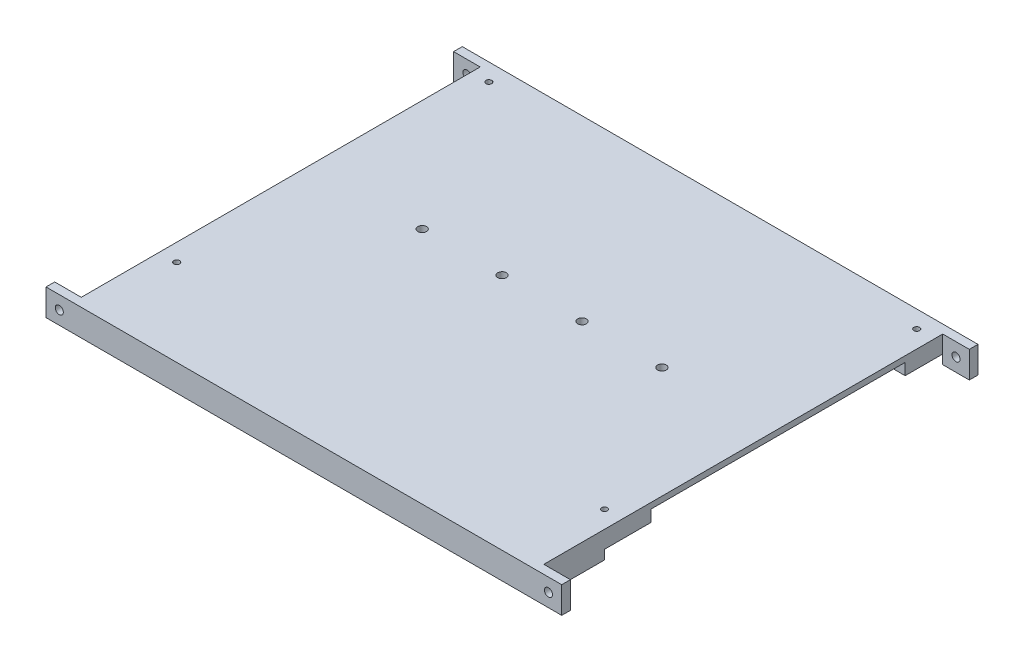
SolidWorks part; units mm, degrees
ref_plane "前视基准面" through (0, 0, 0) normal (0, 0, 1) x (1, 0, 0)
ref_plane "上视基准面" through (0, 0, 0) normal (0, 1, 0) x (1, 0, 0)
ref_plane "右视基准面" through (0, 0, 0) normal (1, 0, 0) x (0, 0, -1)
other "Configuration Table"
sketch "草图1" plane through (0, 0, 0) normal (0, 0, 1) x (1, 0, 0)
  line L61 (-40, 1.5) -> (40, 1.5)
  line L62 (-40, 1.5) -> (-40, -1.5)
  line L63 (-40, -1.5) -> (40, -1.5)
  line L64 (40, 1.5) -> (40, -1.5)
  point P4 (0, 1.5)
  point P5 (-40, 0)
  dimension "D1" = 3
  dimension "D2" = 80
extrude "凸台-拉伸1" add sketch "草图1" along normal blind 60
sketch "草图4" plane through (0, 1.5, 0) normal (0, 1, 0) x (1, 0, 0)
  line L0 (-37, -57) -> (37, -57)
  line L1 (-40, -60) -> (-40, 0) construction
  line L2 (40, -60) -> (-40, -60) construction
  line L9 (40, 0) -> (-40, 0) construction
  line L10 (40, -60) -> (40, 0) construction
  circle A0 centre (-37, -57) radius 0.5
  circle A1 centre (37, -57) radius 0.5
  circle A4 centre (-37, -3) radius 0.5
  circle A5 centre (37, -3) radius 0.5
  point P6 (0, -57)
  point P21 (0, 0)
  dimension "D1" = 1
  dimension "D2" = 3
  dimension "D3" = 3
  dimension "D4" = 3
  dimension "D8" = 3
  dimension "D9" = 3
  dimension "D10" = 3
extrude "切除-拉伸1" cut sketch "草图4" against normal through all contours A0 | A1 | A5 | A4
sketch "草图5" plane through (0, -1.5, 0) normal (0, -1, 0) x (1, 0, 0)
  line L0 (-40, 60) -> (40, 60) construction
  line L1 (-32, 60) -> (32, 60)
  line L2 (-32, 60) -> (-32, 54)
  line L3 (-32, 54) -> (32, 54)
  line L4 (32, 60) -> (32, 54)
  line L5 (40, 60) -> (40, 0) construction
  line L6 (40, 52) -> (34, 52)
  line L7 (40, 52) -> (40, 8)
  line L8 (40, 8) -> (34, 8)
  line L9 (34, 52) -> (34, 8)
  line L10 (-40, 0) -> (40, 0) construction
  line L11 (32, 0) -> (-32, 0)
  line L12 (32, 0) -> (32, 6)
  line L13 (32, 6) -> (-32, 6)
  line L14 (-32, 0) -> (-32, 6)
  line L15 (-40, 60) -> (-40, 0) construction
  line L16 (-40, 8) -> (-34, 8)
  line L17 (-40, 8) -> (-40, 52)
  line L18 (-40, 52) -> (-34, 52)
  line L19 (-34, 8) -> (-34, 52)
  point P24 (-40, 30)
  point P26 (0, 60)
  point P27 (40, 30)
  dimension "D1" = 6
  dimension "D2" = 8
  dimension "D3" = 8
extrude "切除-拉伸4" cut sketch "草图5" against normal blind 2 contours L19 L18 L17 L16 | L3 L4 L1 L2 | L9 L8 L7 L6 | L13 L14 L11 L12
sketch "草图6" plane through (0, 0, 60) normal (0, 0, 1) x (1, 0, 0)
  line L1 (-40, 1.5) -> (40, 1.5)
  line L2 (-40, 1.5) -> (-40, -3.1)
  line L3 (-40, -3.1) -> (40, -3.1)
  line L4 (40, 1.5) -> (40, -3.1)
  line L5 (40, 1.5) -> (44.6, 1.5)
  line L6 (40, 1.5) -> (40, -3.1)
  line L7 (40, -3.1) -> (44.6, -3.1)
  line L8 (44.6, 1.5) -> (44.6, -3.1)
  line L9 (-40, 1.5) -> (-44.6, 1.5)
  line L10 (-40, 1.5) -> (-40, -3.1)
  line L11 (-40, -3.1) -> (-44.6, -3.1)
  line L12 (-44.6, 1.5) -> (-44.6, -3.1)
  circle A0 centre (-42.3, -0.8) radius 0.7
  circle A1 centre (42.3, -0.8) radius 0.7
  point P14 (0, 0)
  point P15 (44.6, -0.8)
  point P16 (42.3, 1.5)
  point P17 (0, 0)
  point P18 (-42.3, 1.5)
  point P19 (-44.6, -0.8)
  line M15 (-32, -1.5) -> (-32, 0.5)
  line M16 (-32, 0.5) -> (32, 0.5)
  line M17 (32, 0.5) -> (32, -1.5)
  line M18 (32, -1.5) -> (40, -1.5)
  line M19 (40, -1.5) -> (40, 1.5)
  line M20 (40, 1.5) -> (-40, 1.5)
  line M21 (-40, 1.5) -> (-40, -1.5)
  line M22 (-40, -1.5) -> (-32, -1.5)
  dimension "D1" = 1.4
extrude "凸台-拉伸2" add sketch "草图6" along normal blind 1.5 from surface contours L9 L12 L11 L2 A0 M21 | L8 L5 L4 L7 A1 M19 region at (-40.0651, 0, 60) region at (42.3, 1.4349, 60) starting at face at (0, -0.25, 0)
extrude "凸台-拉伸3" add sketch "草图6<3>" along normal blind 12 contours L4 L2 L3 M18 M17 M16 M15 M22 | M22 M15 M16 M17 M18 M19 M20 M21 region at (0, 0.5714, 60) region at (0, -1.4, 60)
sketch "草图6<3>" plane through (0, 0, 60) normal (0, 0, 1) x (1, 0, 0) same geometry as "草图6"
extrude "凸台-拉伸4" add sketch "草图6<4>" against normal blind 1.5 from surface contours L9 L12 L11 L2 A0 M21 | L8 L5 L4 L7 A1 M19 region at (-40.0651, 0, 60) region at (42.3, 1.4349, 60) starting at face at (0, -0.8, 72)
sketch "草图6<4>" plane through (0, 0, 60) normal (0, 0, 1) x (1, 0, 0) same geometry as "草图6"
sketch "草图7" plane through (0, 1.5, 0) normal (0, 1, 0) x (1, 0, 0)
  circle A0 centre (20.7375, -30.8) radius 0.75
  circle A1 centre (6.9125, -30.8) radius 0.75
  circle A2 centre (-6.9125, -30.8) radius 0.75
  circle A3 centre (-20.7375, -30.8) radius 0.75
  point P12 (0, 0)
  dimension "D1" = 1.5
extrude "切除-拉伸5" cut sketch "草图7" against normal through all contours A0 | A1 | A2 | A3
